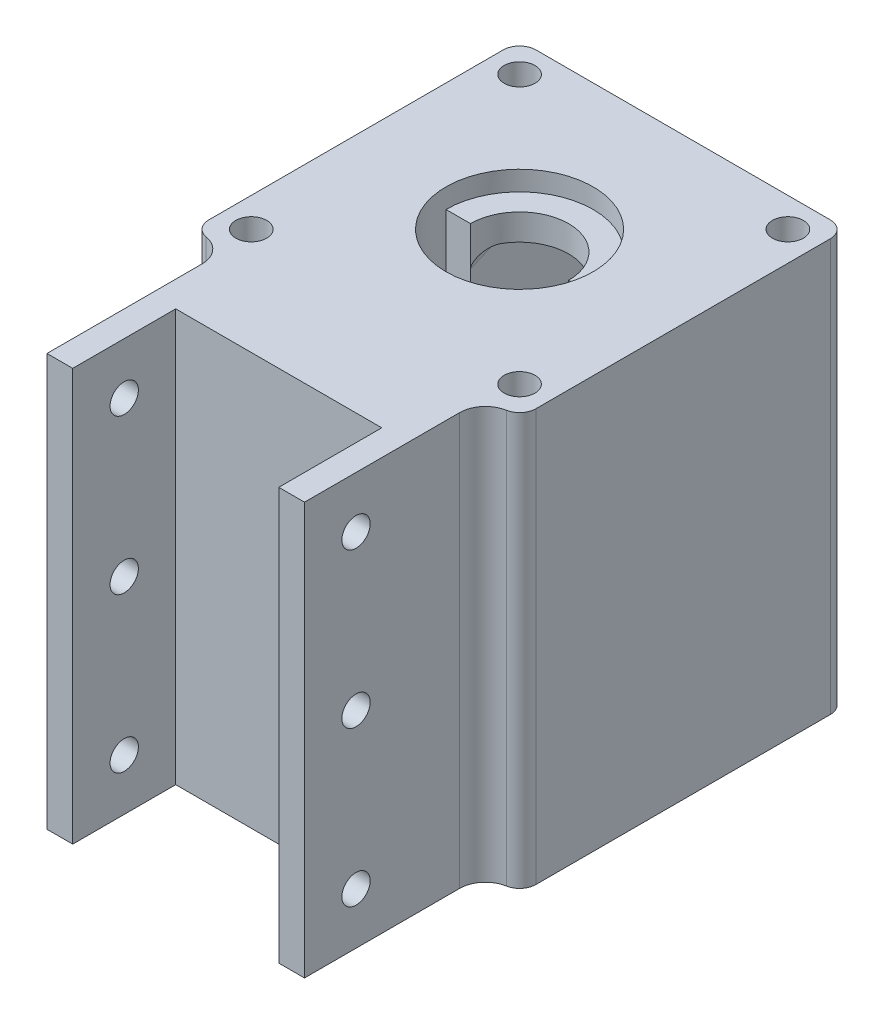
SolidWorks part; units mm, degrees
ref_plane "Front" through (0, 0, 0) normal (0, 0, 1) x (1, 0, 0)
ref_plane "Top" through (0, 0, 0) normal (0, 1, 0) x (1, 0, 0)
ref_plane "Right" through (0, 0, 0) normal (1, 0, 0) x (0, 0, -1)
sketch "Sketch2" plane through (0, 0, 0) normal (0, 1, 0) x (1, 0, 0)
  line L1 (-31.75, 31.75) -> (31.75, 31.75)
  line L2 (-31.75, 31.75) -> (-31.75, -31.75)
  line L3 (-31.75, -31.75) -> (31.75, -31.75)
  line L4 (31.75, 31.75) -> (31.75, -31.75)
  line L5 (-31.75, 31.75) -> (31.75, -31.75) construction
  line L6 (-31.75, -31.75) -> (31.75, 31.75) construction
  point P0 (0, 0)
  dimension "D1" = 63.5
  dimension "D2" = 63.5
extrude "Boss-Extrude1" add sketch "Sketch2" along normal blind 80
sketch "Sketch3" plane through (0, 80, 0) normal (0, 1, 0) x (1, 0, 0)
  line L0 (9.525, 0) -> (14.2875, 0)
  line L1 (-9.525, 0) -> (-14.2875, 0)
  arc A0 (9.525, 0) -> (-9.525, 0) centre (0, 0) ccw
  arc A1 (-14.2875, 0) -> (14.2875, 0) centre (0, 0) ccw
  dimension "D1" = 28.575
  dimension "D2" = 19.05
extrude "Cut-Extrude1" cut sketch "Sketch3" against normal up to next
sketch "Sketch4" plane through (0, 80, 0) normal (0, 1, 0) x (1, 0, 0)
  circle A0 centre (0, 0) radius 14.2875
extrude "Cut-Extrude2" cut sketch "Sketch4" against normal blind 3.81
ref_plane "Plane1" through (0, 71.11, 0) normal (0, 1, 0) x (1, 0, 0)
sketch "Sketch6" plane through (0, 71.11, 0) normal (0, 1, 0) x (1, 0, 0)
  line L0 (0, 0) -> (0, 31.75) construction
  line L1 (31.75, 31.75) -> (-31.75, 31.75) construction
  line L2 (9.525, 0) -> (19.05, 31.75)
  line L3 (19.05, 31.75) -> (-19.05, 31.75)
  line L4 (31.75, -31.75) -> (31.75, 31.75) construction
  line L5 (-9.525, 0) -> (-19.05, 31.75)
  arc A0 (9.525, 0) -> (-9.525, 0) centre (0, 0) ccw construction
  arc A1 (9.525, 0) -> (-9.525, 0) centre (0, 0) ccw
  dimension "D1" = 12.7
extrude "Cut-Extrude3" cut sketch "Sketch6" against normal offset from surface (62.22 mm away) 8.89 up to face at (0, 0, 1.1906)
sketch "Sketch7" plane through (0, 0, 0) normal (1, 0, 0) x (0, 0, -1)
  line L0 (0, 8.89) -> (31.75, 8.89) construction
  line L1 (0, 8.89) -> (31.75, 8.89)
  line L2 (0, 8.89) -> (0, 0)
  line L3 (0, 0) -> (31.75, 8.89)
extrude "Cut-Extrude4" cut sketch "Sketch7" against normal up to surface and the other way up to surface up to face at (-14.2875, 40, -15.875) other way up to face at (14.2875, 40, -15.875)
fillet "Fillet2" radius 2.54 5 edges at (14.2875, 71.11, -15.875) (-14.2875, 71.11, -15.875) (0, 2.667, -9.525) (-14.2875, 4.445, -15.875) (14.2875, 4.445, -15.875)
sketch "Sketch9" plane through (0, 0, 31.75) normal (0, 0, 1) x (1, 0, 0)
  line L0 (0, 80) -> (0, 0) construction
  line L1 (-31.75, 80) -> (31.75, 80) construction
  line L2 (-31.75, 0) -> (31.75, 0) construction
  line L3 (-20, 80) -> (-25, 80)
  line L4 (-20, 80) -> (-20, 0)
  line L5 (-20, 0) -> (-25, 0)
  line L6 (-25, 80) -> (-25, 0)
  line L7 (-20, 80) -> (-25, 0) construction
  line L8 (-20, 0) -> (-25, 80) construction
  line L9 (20, 0) -> (25, 80) construction
  line L10 (20, 80) -> (25, 0) construction
  line L11 (25, 80) -> (25, 0)
  line L12 (20, 0) -> (25, 0)
  line L13 (20, 80) -> (20, 0)
  line L14 (20, 80) -> (25, 80)
  point P9 (-22.5, 40)
  point P16 (22.5, 40)
  dimension "D1" = 5
  dimension "D2" = 20
extrude "Boss-Extrude2" add sketch "Sketch9" along normal blind 35
sketch "Sketch10" plane through (-25, 0, 0) normal (-1, 0, 0) x (0, 0, 1)
  line L0 (56.75, 80) -> (56.75, 0) construction
  line L1 (66.75, 80) -> (31.75, 80) construction
  line L2 (66.75, 0) -> (31.75, 0) construction
  line L3 (66.75, 80) -> (66.75, 0) construction
  circle A0 centre (56.75, 70) radius 2.75
  circle A1 centre (56.75, 10) radius 2.75
  circle A2 centre (56.75, 40) radius 2.75
  dimension "D1" = 5.5
  dimension "D2" = 10
  dimension "D3" = 10
  dimension "D4" = 10
extrude "Cut-Extrude6" cut sketch "Sketch10" against normal through all
sketch "Sketch11" plane through (0, 0, 0) normal (0, -1, 0) x (1, 0, 0)
  circle A0 centre (26.0427, -26.0427) radius 3
  circle A1 centre (26.0427, 26.0427) radius 3
  circle A2 centre (-26.0427, -26.0427) radius 3
  circle A3 centre (-26.0427, 26.0427) radius 3
  dimension "D1" = 6
extrude "Cut-Extrude7" cut sketch "Sketch11" against normal up to next
sketch "Sketch12" plane through (0, 0, 31.75) normal (0, 0, 1) x (1, 0, 0)
  line L4 (20, 0) -> (20, 80)
  line L5 (20, 80) -> (-20, 80)
  line L6 (-20, 80) -> (-20, 0)
  line L7 (-20, 0) -> (20, 0)
  line L8 (20, 0) -> (20, 80)
  line L9 (20, 80) -> (-20, 80)
  line L10 (-20, 80) -> (-20, 0)
  line L11 (-20, 0) -> (20, 0)
  dimension "D1" = 0
extrude "Boss-Extrude3" add sketch "Sketch12" along normal offset from surface (15 mm away) 20 up to face at (-22.5, 40, 66.75)
sketch "Sketch13" plane through (0, 0, -31.75) normal (0, 0, -1) x (-1, 0, 0)
  line L0 (0, 80) -> (0, 0) construction
  line L1 (-31.75, 80) -> (31.75, 80) construction
  line L2 (-31.75, 0) -> (31.75, 0) construction
  line L3 (-31.75, 40) -> (31.75, 40) construction
  line L4 (-31.75, 80) -> (-31.75, 0) construction
  line L5 (31.75, 80) -> (31.75, 0) construction
  circle A0 centre (-18.75, 75) radius 3
  circle A1 centre (18.75, 75) radius 3
  circle A2 centre (18.75, 5) radius 3
  circle A3 centre (-18.75, 5) radius 3
  dimension "D1" = 6
  dimension "D2" = 13
  dimension "D3" = 5
extrude "Cut-Extrude8" cut sketch "Sketch13" against normal blind 10
fillet "Fillet3" radius 3.175 4 edges at (31.75, 40, -31.75) (-31.75, 40, -31.75) (-31.75, 40, 31.75) (31.75, 40, 31.75)
fillet "Fillet4" radius 5 2 edges at (25, 40, 31.75) (-25, 40, 31.75)
